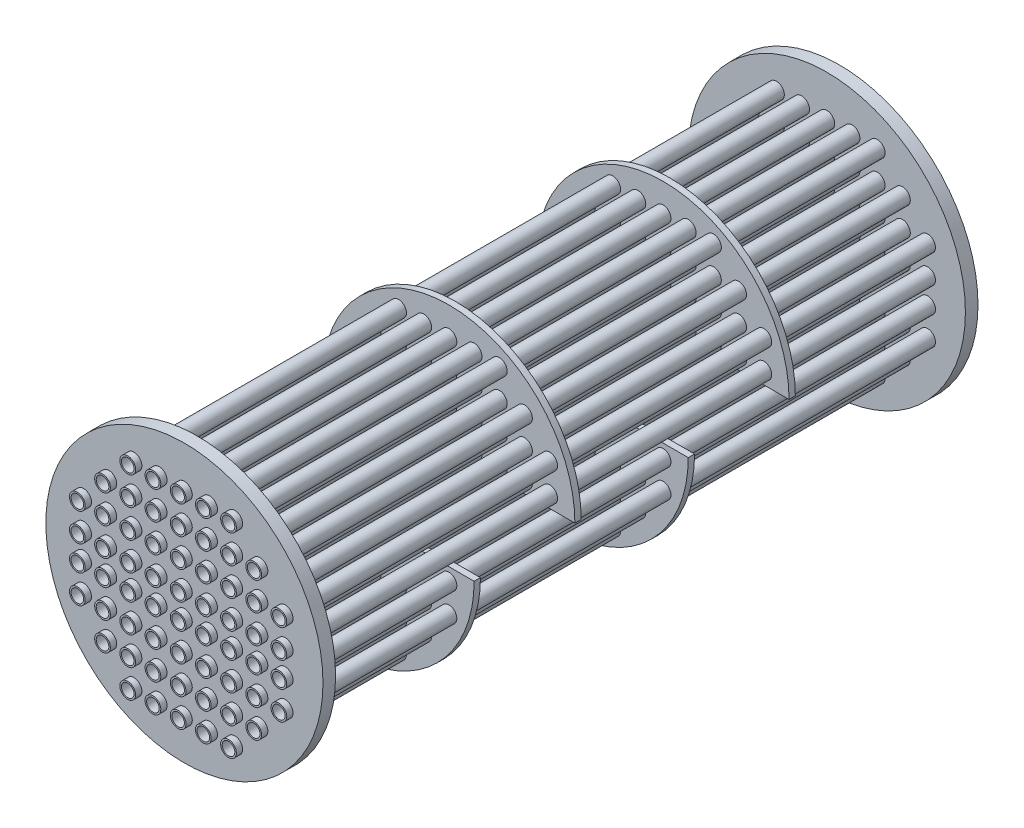
SolidWorks part; units mm, degrees
ref_plane "Front Plane" through (0, 0, 0) normal (0, 0, 1) x (1, 0, 0)
ref_plane "Top Plane" through (0, 0, 0) normal (0, 1, 0) x (1, 0, 0)
ref_plane "Right Plane" through (0, 0, 0) normal (1, 0, 0) x (0, 0, -1)
ref_plane "Plane1" through (0, 0, -1000) normal (0, 0, 1) x (1, 0, 0)
ref_plane "Plane2" through (0, 0, -750) normal (0, 0, 1) x (1, 0, 0)
ref_plane "Plane3" through (0, 0, -250) normal (0, 0, 1) x (1, 0, 0)
ref_plane "Plane4" through (0, 0, -410) normal (0, 0, 1) x (1, 0, 0)
ref_plane "Plane5" through (0, 0, -590) normal (0, 0, 1) x (1, 0, 0)
sketch "Sketch1" plane through (0, 0, 0) normal (0, 0, 1) x (1, 0, 0)
  circle A0 centre (0, 0) radius 220
  dimension "D1" = 440
extrude "Boss-Extrude1" add sketch "Sketch1" along normal blind 20
sketch "Sketch3" plane through (0, 0, -1000) normal (0, 0, 1) x (1, 0, 0)
  circle A1 centre (0, 0) radius 220
  circle A2 centre (0, 0) radius 220
  dimension "D1" = 0
extrude "Boss-Extrude2" add sketch "Sketch3" against normal blind 20 separate body
sketch "Sketch4" plane through (0, 0, -250) normal (0, 0, 1) x (1, 0, 0)
  line L0 (-200, 0) -> (200, 0)
  arc A0 (-200, 0) -> (200, 0) centre (0, 0) ccw
  dimension "D1" = 400
extrude "Boss-Extrude3" add sketch "Sketch4" along normal blind 10 separate body
sketch "Sketch5" plane through (0, 0, -410) normal (0, 0, 1) x (1, 0, 0)
  line L0 (-200, 0) -> (200, 0)
  arc A0 (200, 0) -> (-200, 0) centre (0, 0) ccw
  dimension "D1" = 400
extrude "Boss-Extrude4" add sketch "Sketch5" along normal blind 10 separate body
sketch "Sketch6" plane through (0, 0, -590) normal (0, 0, 1) x (1, 0, 0)
  line L1 (200, 0) -> (-200, 0)
  line L2 (200, 0) -> (-200, 0)
  arc A1 (-200, 0) -> (200, 0) centre (0, 0) ccw
  arc A2 (-200, 0) -> (200, 0) centre (0, 0) ccw
  dimension "D1" = 0
extrude "Boss-Extrude5" add sketch "Sketch6" along normal blind 10 separate body
sketch "Sketch8" plane through (0, 0, -750) normal (0, 0, 1) x (1, 0, 0)
  line L1 (-200, 0) -> (200, 0)
  line L2 (-200, 0) -> (200, 0)
  arc A1 (200, 0) -> (-200, 0) centre (0, 0) ccw
  arc A2 (200, 0) -> (-200, 0) centre (0, 0) ccw
  dimension "D1" = 0
extrude "Boss-Extrude6" add sketch "Sketch8" along normal blind 10 separate body
sketch "Sketch9" plane through (0, 0, 20) normal (0, 0, 1) x (1, 0, 0)
  line L0 (0, -20) -> (0, 20) construction
  line L3 (0, -20) -> (0, -220) construction
  circle A2 centre (0, 20) radius 12.5
  circle A22 centre (0, 20) radius 10
  circle A129 centre (0, 65) radius 10
  circle A132 centre (0, 65) radius 12.5
  circle A133 centre (0, 110) radius 10
  circle A134 centre (0, 110) radius 12.5
  circle A135 centre (0, 155) radius 10
  circle A136 centre (0, 155) radius 12.5
  circle A143 centre (40, 20) radius 10
  circle A144 centre (40, 20) radius 12.5
  circle A145 centre (40, 65) radius 10
  circle A146 centre (40, 65) radius 12.5
  circle A147 centre (40, 110) radius 10
  circle A148 centre (40, 110) radius 12.5
  circle A149 centre (40, 155) radius 10
  circle A150 centre (40, 155) radius 12.5
  circle A153 centre (80, 20) radius 10
  circle A154 centre (80, 20) radius 12.5
  circle A155 centre (80, 65) radius 10
  circle A156 centre (80, 65) radius 12.5
  circle A157 centre (80, 110) radius 10
  circle A158 centre (80, 110) radius 12.5
  circle A159 centre (80, 155) radius 10
  circle A160 centre (80, 155) radius 12.5
  circle A163 centre (120, 20) radius 10
  circle A164 centre (120, 20) radius 12.5
  circle A165 centre (120, 65) radius 10
  circle A166 centre (120, 65) radius 12.5
  circle A167 centre (120, 110) radius 10
  circle A168 centre (120, 110) radius 12.5
  circle A173 centre (160, 20) radius 10
  circle A174 centre (160, 20) radius 12.5
  circle A175 centre (160, 65) radius 10
  circle A176 centre (160, 65) radius 12.5
  circle A201 centre (160, 155) radius 10 [skipped]
  circle A202 centre (160, 155) radius 12.5 [skipped]
  circle A203 centre (200, 65) radius 10 [skipped]
  circle A204 centre (200, 65) radius 12.5 [skipped]
  circle A205 centre (200, 110) radius 10 [skipped]
  circle A206 centre (200, 110) radius 12.5 [skipped]
  circle A207 centre (200, 155) radius 10 [skipped]
  circle A208 centre (200, 155) radius 12.5 [skipped]
  circle A212 centre (-160, 65) radius 12.5
  circle A213 centre (-160, 65) radius 10
  circle A214 centre (-160, 20) radius 12.5
  circle A215 centre (-160, 20) radius 10
  circle A218 centre (-120, 110) radius 12.5
  circle A219 centre (-120, 110) radius 10
  circle A220 centre (-120, 65) radius 12.5
  circle A221 centre (-120, 65) radius 10
  circle A222 centre (-120, 20) radius 12.5
  circle A223 centre (-120, 20) radius 10
  circle A224 centre (-80, 155) radius 12.5
  circle A225 centre (-80, 155) radius 10
  circle A226 centre (-80, 110) radius 12.5
  circle A227 centre (-80, 110) radius 10
  circle A228 centre (-80, 65) radius 12.5
  circle A229 centre (-80, 65) radius 10
  circle A230 centre (-80, 20) radius 12.5
  circle A231 centre (-80, 20) radius 10
  circle A234 centre (-40, 155) radius 12.5
  circle A235 centre (-40, 155) radius 10
  circle A236 centre (-40, 110) radius 12.5
  circle A237 centre (-40, 110) radius 10
  circle A238 centre (-40, 65) radius 12.5
  circle A239 centre (-40, 65) radius 10
  circle A240 centre (-40, 20) radius 12.5
  circle A241 centre (-40, 20) radius 10
  circle A242 centre (-40, -20) radius 10
  circle A243 centre (-40, -20) radius 12.5
  circle A244 centre (-40, -65) radius 10
  circle A245 centre (-40, -65) radius 12.5
  circle A246 centre (-40, -110) radius 10
  circle A247 centre (-40, -110) radius 12.5
  circle A248 centre (-40, -155) radius 10
  circle A249 centre (-40, -155) radius 12.5
  circle A252 centre (-80, -20) radius 10
  circle A253 centre (-80, -20) radius 12.5
  circle A254 centre (-80, -65) radius 10
  circle A255 centre (-80, -65) radius 12.5
  circle A256 centre (-80, -110) radius 10
  circle A257 centre (-80, -110) radius 12.5
  circle A258 centre (-80, -155) radius 10
  circle A259 centre (-80, -155) radius 12.5
  circle A260 centre (-120, -20) radius 10
  circle A261 centre (-120, -20) radius 12.5
  circle A262 centre (-120, -65) radius 10
  circle A263 centre (-120, -65) radius 12.5
  circle A264 centre (-120, -110) radius 10
  circle A265 centre (-120, -110) radius 12.5
  circle A268 centre (-160, -20) radius 10
  circle A269 centre (-160, -20) radius 12.5
  circle A270 centre (-160, -65) radius 10
  circle A271 centre (-160, -65) radius 12.5
  circle A279 centre (160, -65) radius 12.5
  circle A280 centre (160, -65) radius 10
  circle A281 centre (160, -20) radius 12.5
  circle A282 centre (160, -20) radius 10
  circle A285 centre (120, -110) radius 12.5
  circle A286 centre (120, -110) radius 10
  circle A287 centre (120, -65) radius 12.5
  circle A288 centre (120, -65) radius 10
  circle A289 centre (120, -20) radius 12.5
  circle A290 centre (120, -20) radius 10
  circle A291 centre (80, -155) radius 12.5
  circle A292 centre (80, -155) radius 10
  circle A293 centre (80, -110) radius 12.5
  circle A294 centre (80, -110) radius 10
  circle A295 centre (80, -65) radius 12.5
  circle A296 centre (80, -65) radius 10
  circle A297 centre (80, -20) radius 12.5
  circle A298 centre (80, -20) radius 10
  circle A301 centre (40, -155) radius 12.5
  circle A302 centre (40, -155) radius 10
  circle A303 centre (40, -110) radius 12.5
  circle A304 centre (40, -110) radius 10
  circle A305 centre (40, -65) radius 12.5
  circle A306 centre (40, -65) radius 10
  circle A307 centre (40, -20) radius 12.5
  circle A308 centre (40, -20) radius 10
  circle A311 centre (0, -155) radius 12.5
  circle A312 centre (0, -155) radius 10
  circle A313 centre (0, -110) radius 12.5
  circle A314 centre (0, -110) radius 10
  circle A315 centre (0, -65) radius 12.5
  circle A317 centre (0, -65) radius 10
  circle A318 centre (0, -20) radius 10
  circle A319 centre (0, -20) radius 12.5
  circle A320 centre (0, 200) radius 10 [skipped]
  circle A321 centre (0, 200) radius 12.5 [skipped]
  circle A322 centre (200, 20) radius 10 [skipped]
  circle A323 centre (200, 20) radius 12.5 [skipped]
  circle A324 centre (120, 155) radius 10 [skipped]
  circle A325 centre (120, 155) radius 12.5 [skipped]
  circle A326 centre (160, 110) radius 10 [skipped]
  circle A327 centre (160, 110) radius 12.5 [skipped]
  point P148 (0, 0)
  point P266 (0, 0)
  point P267 (0, 0)
  dimension "D4" = 5
extrude "Cut-Extrude1" cut sketch "Sketch9" against normal through all contours A213 | A219 | A221 | A225 | A227 | A229 | A239 | A237 | A235 | A135 | A133 | A129 | A22 | A241 | A231 | A223 | A215 | A268 | A270 | A264 | A262 | A260 | A254 | A256 | A258 | A248 | A246 | A244 | A242 | A318 | A317 | A314 | A312 | A302 | A304 | A306 | A308 | A298 | A296 | A294 | A292 | A286 | A288 | A280 | A290 | A282 | A149 | A159 | A147 | A145 | A143 | A153 | A155 | A165 | A163 | A157 | A167 | A175 | A173 | A252 region at (0, 20, 20) region at (0, 65, 20) region at (0, 110, 20) region at (0, 155, 20) region at (40, 20, 20) region at (40, 65, 20) region at (40, 110, 20) region at (40, 155, 20) region at (80, 20, 20) region at (80, 65, 20) region at (80, 110, 20) region at (80, 155, 20) region at (120, 20, 20) region at (120, 65, 20) region at (120, 110, 20) region at (160, 20, 20) region at (160, 65, 20) region at (-160, 65, 20) region at (-160, 20, 20) region at (-120, 110, 20) region at (-120, 65, 20) region at (-120, 20, 20) region at (-80, 155, 20) region at (-80, 110, 20) region at (-80, 65, 20) region at (-80, 20, 20) region at (-40, 155, 20) region at (-40, 110, 20) region at (-40, 65, 20) region at (-40, 20, 20) region at (-40, -20, 20) region at (-40, -65, 20) region at (-40, -110, 20) region at (-40, -155, 20) region at (-80, -65, 20) region at (-80, -110, 20) region at (-80, -155, 20) region at (-120, -20, 20) region at (-120, -65, 20) region at (-120, -110, 20) region at (-160, -20, 20) region at (-160, -65, 20) region at (160, -65, 20) region at (160, -20, 20) region at (120, -110, 20) region at (120, -65, 20) region at (120, -20, 20) region at (80, -155, 20) region at (80, -110, 20) region at (80, -65, 20) region at (80, -20, 20) region at (40, -155, 20) region at (40, -110, 20) region at (40, -65, 20) region at (40, -20, 20) region at (0, -155, 20) region at (0, -110, 20) region at (0, -65, 20) region at (0, -20, 20)
ref_plane "Plane6" through (0, 0, 30) normal (0, 0, 1) x (1, 0, 0)
sketch "Sketch10" plane through (0, 0, 30) normal (0, 0, 1) x (1, 0, 0)
  line L0 (2.5, -267.9625) -> (2.5, 267.9625)
  line L3 (0, -267.9625) -> (0, 267.9625) construction
  circle A46 centre (-80, -155) radius 10 construction
  circle A47 centre (-80, -155) radius 10
  circle A48 centre (-40, -155) radius 10 construction
  circle A49 centre (0, -155) radius 10 construction
  circle A50 centre (-40, -155) radius 10
  circle A51 centre (0, -155) radius 10
  circle A52 centre (80, -155) radius 10 construction
  circle A53 centre (40, -155) radius 10 construction
  circle A185 centre (80, -155) radius 10
  circle A186 centre (40, -155) radius 10
  circle A187 centre (-80, 20) radius 10 construction
  circle A188 centre (-40, 20) radius 10 construction
  circle A189 centre (0, 20) radius 10 construction
  circle A190 centre (-80, 20) radius 10
  circle A191 centre (-40, 20) radius 10
  circle A192 centre (0, 20) radius 10
  circle A372 centre (-80, -110) radius 10 construction
  circle A373 centre (-120, -110) radius 10 construction
  circle A374 centre (-120, -65) radius 10 construction
  circle A376 centre (-120, -20) radius 10 construction
  circle A377 centre (-160, -65) radius 10 construction
  circle A378 centre (-160, -20) radius 10 construction
  circle A379 centre (-160, 20) radius 10 construction
  circle A380 centre (-120, 20) radius 10 construction
  circle A381 centre (-80, -110) radius 10
  circle A382 centre (-120, -110) radius 10
  circle A383 centre (-120, -65) radius 10
  circle A384 centre (-120, -20) radius 10
  circle A385 centre (-160, -65) radius 10
  circle A386 centre (-160, -20) radius 10
  circle A387 centre (-160, 20) radius 10
  circle A388 centre (-120, 20) radius 10
  circle A389 centre (-40, -110) radius 10 construction
  circle A390 centre (0, -110) radius 10 construction
  circle A391 centre (0, -65) radius 10 construction
  circle A392 centre (0, -20) radius 10 construction
  circle A393 centre (-40, -20) radius 10 construction
  circle A394 centre (-40, -65) radius 10 construction
  circle A395 centre (-80, -65) radius 10 construction
  circle A396 centre (-80, -20) radius 10 construction
  circle A397 centre (-40, -110) radius 10
  circle A398 centre (0, -110) radius 10
  circle A399 centre (0, -65) radius 10
  circle A400 centre (0, -20) radius 10
  circle A401 centre (-40, -20) radius 10
  circle A402 centre (-40, -65) radius 10
  circle A403 centre (-80, -65) radius 10
  circle A404 centre (-80, -20) radius 10
  circle A405 centre (160, -20) radius 10 construction
  circle A406 centre (160, 20) radius 10 construction
  circle A407 centre (120, 20) radius 10 construction
  circle A408 centre (80, 20) radius 10 construction
  circle A409 centre (80, -20) radius 10 construction
  circle A410 centre (40, -110) radius 10 construction
  circle A411 centre (40, -65) radius 10 construction
  circle A412 centre (40, -20) radius 10 construction
  circle A413 centre (40, 20) radius 10 construction
  circle A414 centre (160, -20) radius 10
  circle A415 centre (160, 20) radius 10
  circle A416 centre (120, 20) radius 10
  circle A417 centre (80, 20) radius 10
  circle A418 centre (80, -20) radius 10
  circle A419 centre (40, -110) radius 10
  circle A420 centre (40, -65) radius 10
  circle A421 centre (40, -20) radius 10
  circle A422 centre (40, 20) radius 10
  circle A423 centre (160, -65) radius 10 construction
  circle A424 centre (120, -65) radius 10 construction
  circle A425 centre (120, -110) radius 10 construction
  circle A426 centre (80, -110) radius 10 construction
  circle A427 centre (80, -65) radius 10 construction
  circle A428 centre (120, -20) radius 10 construction
  circle A429 centre (160, -65) radius 10
  circle A430 centre (120, -65) radius 10
  circle A431 centre (120, -110) radius 10
  circle A432 centre (80, -110) radius 10
  circle A433 centre (80, -65) radius 10
  circle A434 centre (120, -20) radius 10
  circle A435 centre (-120, 65) radius 10 construction
  circle A436 centre (-160, 65) radius 10 construction
  circle A437 centre (-80, 65) radius 10 construction
  circle A438 centre (-40, 65) radius 10 construction
  circle A439 centre (0, 65) radius 10 construction
  circle A440 centre (40, 65) radius 10 construction
  circle A441 centre (80, 65) radius 10 construction
  circle A442 centre (120, 65) radius 10 construction
  circle A443 centre (160, 65) radius 10 construction
  circle A444 centre (-120, 65) radius 10
  circle A445 centre (-160, 65) radius 10
  circle A446 centre (-80, 65) radius 10
  circle A447 centre (-40, 65) radius 10
  circle A448 centre (0, 65) radius 10
  circle A449 centre (40, 65) radius 10
  circle A450 centre (80, 65) radius 10
  circle A451 centre (120, 65) radius 10
  circle A452 centre (160, 65) radius 10
  circle A453 centre (-120, 110) radius 10 construction
  circle A454 centre (-80, 110) radius 10 construction
  circle A455 centre (-40, 110) radius 10 construction
  circle A456 centre (0, 110) radius 10 construction
  circle A457 centre (40, 110) radius 10 construction
  circle A458 centre (80, 110) radius 10 construction
  circle A459 centre (120, 110) radius 10 construction
  circle A460 centre (-120, 110) radius 10
  circle A461 centre (-80, 110) radius 10
  circle A462 centre (-40, 110) radius 10
  circle A463 centre (0, 110) radius 10
  circle A464 centre (40, 110) radius 10
  circle A465 centre (80, 110) radius 10
  circle A466 centre (120, 110) radius 10
  circle A467 centre (80, 155) radius 10 construction
  circle A468 centre (40, 155) radius 10 construction
  circle A469 centre (0, 155) radius 10 construction
  circle A470 centre (-40, 155) radius 10 construction
  circle A471 centre (-80, 155) radius 10 construction
  circle A472 centre (80, 155) radius 10
  circle A473 centre (40, 155) radius 10
  circle A474 centre (0, 155) radius 10
  circle A475 centre (-40, 155) radius 10
  circle A476 centre (-80, 155) radius 10
  circle A477 centre (-80, -155) radius 12.5
  circle A478 centre (-40, -155) radius 12.5
  circle A479 centre (0, -155) radius 12.5
  circle A480 centre (80, -155) radius 12.5
  circle A481 centre (40, -155) radius 12.5
  circle A482 centre (-80, 20) radius 12.5
  circle A483 centre (-40, 20) radius 12.5
  circle A484 centre (0, 20) radius 12.5
  circle A485 centre (-80, -110) radius 12.5
  circle A486 centre (-120, -110) radius 12.5
  circle A487 centre (-120, -65) radius 12.5
  circle A488 centre (-120, -20) radius 12.5
  circle A489 centre (-160, -65) radius 12.5
  circle A490 centre (-160, -20) radius 12.5
  circle A491 centre (-160, 20) radius 12.5
  circle A492 centre (-120, 20) radius 12.5
  circle A493 centre (-40, -110) radius 12.5
  circle A494 centre (0, -110) radius 12.5
  circle A495 centre (0, -65) radius 12.5
  circle A496 centre (0, -20) radius 12.5
  circle A497 centre (-40, -20) radius 12.5
  circle A498 centre (-40, -65) radius 12.5
  circle A499 centre (-80, -65) radius 12.5
  circle A500 centre (-80, -20) radius 12.5
  circle A501 centre (160, -20) radius 12.5
  circle A502 centre (160, 20) radius 12.5
  circle A503 centre (120, 20) radius 12.5
  circle A504 centre (80, 20) radius 12.5
  circle A505 centre (80, -20) radius 12.5
  circle A506 centre (40, -110) radius 12.5
  circle A507 centre (40, -65) radius 12.5
  circle A508 centre (40, -20) radius 12.5
  circle A509 centre (40, 20) radius 12.5
  circle A510 centre (160, -65) radius 12.5
  circle A511 centre (120, -65) radius 12.5
  circle A512 centre (120, -110) radius 12.5
  circle A513 centre (80, -110) radius 12.5
  circle A514 centre (80, -65) radius 12.5
  circle A515 centre (120, -20) radius 12.5
  circle A516 centre (-120, 65) radius 12.5
  circle A517 centre (-160, 65) radius 12.5
  circle A518 centre (-80, 65) radius 12.5
  circle A519 centre (-40, 65) radius 12.5
  circle A520 centre (0, 65) radius 12.5
  circle A521 centre (40, 65) radius 12.5
  circle A522 centre (80, 65) radius 12.5
  circle A523 centre (120, 65) radius 12.5
  circle A524 centre (160, 65) radius 12.5
  circle A525 centre (-120, 110) radius 12.5
  circle A526 centre (-80, 110) radius 12.5
  circle A527 centre (-40, 110) radius 12.5
  circle A528 centre (0, 110) radius 12.5
  circle A529 centre (40, 110) radius 12.5
  circle A530 centre (80, 110) radius 12.5
  circle A531 centre (120, 110) radius 12.5
  circle A532 centre (80, 155) radius 12.5
  circle A533 centre (40, 155) radius 12.5
  circle A534 centre (0, 155) radius 12.5
  circle A535 centre (-40, 155) radius 12.5
  circle A536 centre (-80, 155) radius 12.5
  dimension "D1" = 2.5
extrude "Boss-Extrude8" add sketch "Sketch10" against normal blind 1060 separate body contours A477 A47 | A478 A50 | A479 L3 A51 | L0 A479 A51 | L3 A51 L0 A479 | L3 A479 L0 A51 | A481 A186 | A480 A185 | A486 A382 | A485 A381 | A493 A397 | A494 L3 A398 | L3 A398 L0 A494 | L3 A494 L0 A398 | L0 A494 A398 | A506 A419 | A513 A432 | A510 A429 | A511 A430 | A514 A433 | A507 A420 | L0 A495 A399 | L3 A495 L0 A399 | A495 L3 A399 | L3 A399 L0 A495 | A498 A402 | A499 A403 | A489 A385 | A487 A383 | A490 A386 | A488 A384 | A500 A404 | A497 A401 | L3 A400 L0 A496 | A496 L3 A400 | L0 A496 A400 | L3 A496 L0 A400 | A508 A421 | A505 A418 | A501 A414 | L3 A192 L0 A484 | A484 L3 A192 | L0 A484 A192 | L3 A484 L0 A192 | A509 A422 | A504 A417 | A503 A416 | A502 A415 | A492 A388 | A483 A191 | L3 A448 L0 A520 | A520 L3 A448 | L0 A520 A448 | L3 A520 L0 A448 | A521 A449 | A522 A450 | A519 A447 | A518 A446 | A516 A444 | A517 A445 | A523 A451 | A524 A452 | L3 A463 L0 A528 | A528 L3 A463 | L0 A528 A463 | L3 A528 L0 A463 | A529 A464 | A530 A465 | A531 A466 | A527 A462 | A526 A461 | A525 A460 | A536 A476 | A535 A475 | L3 A474 L0 A534 | A534 L3 A474 | L0 A534 A474 | L3 A534 L0 A474 | A533 A473 | A532 A472 | A491 A387 | A482 A190 | A515 A434 | A512 A431 region at (1.2553, -166.1548, 30) region at (2.7646, -165.965, 30) region at (-12.2205, -155, 30) region at (1.2553, -143.8452, 30) region at (-12.2205, -110, 30) region at (1.2553, -121.1548, 30) region at (2.7646, -120.965, 30) region at (1.2553, -98.8452, 30) region at (-12.2205, -65, 30) region at (1.2553, -76.1548, 30) region at (1.2553, -53.8452, 30) region at (2.7646, -75.965, 30) region at (-12.2205, -20, 30) region at (1.2553, -31.1548, 30) region at (1.2553, -8.8452, 30) region at (2.7646, -30.965, 30) region at (-12.2205, 20, 30) region at (1.2553, 8.8452, 30) region at (1.2553, 31.1548, 30) region at (2.7646, 9.035, 30) region at (-12.2205, 65, 30) region at (1.2553, 53.8452, 30) region at (1.2553, 76.1548, 30) region at (2.7646, 54.035, 30) region at (-12.2205, 110, 30) region at (1.2553, 98.8452, 30) region at (1.2553, 121.1548, 30) region at (2.7646, 99.035, 30) region at (-12.2205, 155, 30) region at (1.2553, 143.8452, 30) region at (1.2553, 166.1548, 30) region at (2.7646, 144.035, 30) region at (-92.1464, -155, 30) region at (-52.1464, -155, 30) region at (67.8536, -155, 30) region at (27.8536, -155, 30) region at (-92.1464, 20, 30) region at (-52.1464, 20, 30) region at (-92.1464, -110, 30) region at (-132.1464, -110, 30) region at (-132.1464, -65, 30) region at (-132.1464, -20, 30) region at (-172.1464, -65, 30) region at (-172.1464, -20, 30) region at (-172.1464, 20, 30) region at (-132.1464, 20, 30) region at (-52.1464, -110, 30) region at (-52.1464, -20, 30) region at (-52.1464, -65, 30) region at (-92.1464, -65, 30) region at (-92.1464, -20, 30) region at (147.8536, -20, 30) region at (147.8536, 20, 30) region at (107.8536, 20, 30) region at (67.8536, 20, 30) region at (67.8536, -20, 30) region at (27.8536, -110, 30) region at (27.8536, -65, 30) region at (27.8536, -20, 30) region at (27.8536, 20, 30)
